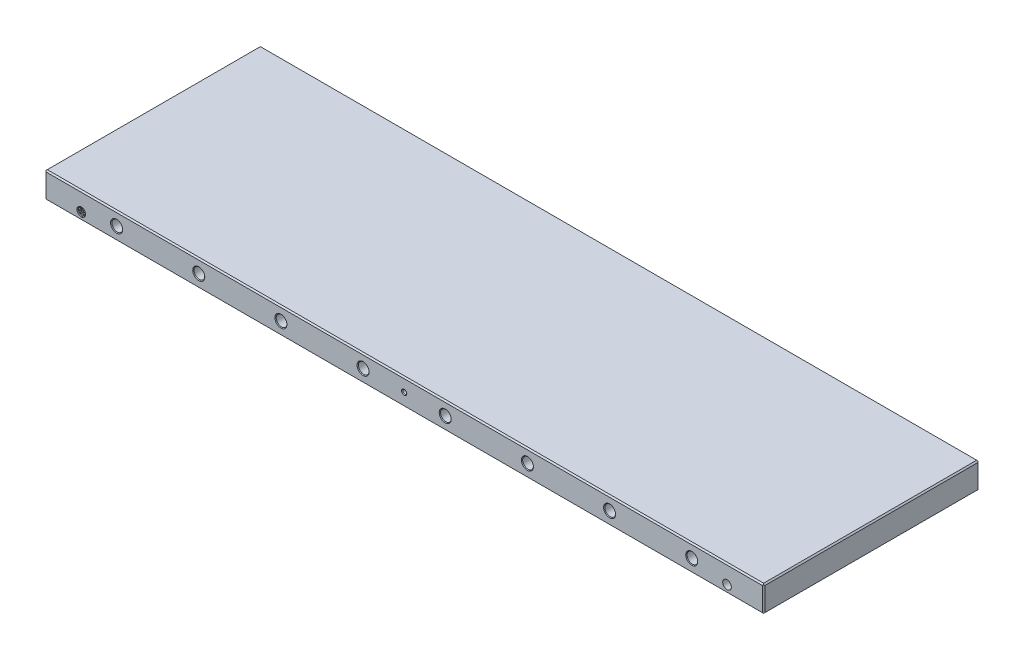
SolidWorks part; units mm, degrees
ref_plane "Front Plane" through (0, 0, 0) normal (0, 0, 1) x (1, 0, 0)
ref_plane "Top Plane" through (0, 0, 0) normal (0, 1, 0) x (1, 0, 0)
ref_plane "Right Plane" through (0, 0, 0) normal (1, 0, 0) x (0, 0, -1)
sketch "Sketch1" plane through (0, 0, 0) normal (0, 1, 0) x (1, 0, 0)
  line L1 (-275, 82.5) -> (275, 82.5)
  line L2 (-275, 82.5) -> (-275, -82.5)
  line L3 (-275, -82.5) -> (275, -82.5)
  line L4 (275, 82.5) -> (275, -82.5)
  line L5 (-275, 82.5) -> (275, -82.5) construction
  line L6 (-275, -82.5) -> (275, 82.5) construction
  point P0 (0, 0)
  dimension "D1" = 165
  dimension "D2" = 550
extrude "Boss-Extrude1" add sketch "Sketch1" along normal blind 20
sketch "Sketch2" plane through (0, 0, 82.5) normal (0, 0, 1) x (1, 0, 0)
  line L0 (-275, 10) -> (275, 10) construction
  line L1 (-275, 20) -> (-275, 0) construction
  line L2 (275, 20) -> (275, 0) construction
  circle A0 centre (-220, 10) radius 4.1
  circle A1 centre (-157.1429, 10) radius 4.1
  circle A2 centre (-94.2857, 10) radius 4.1
  circle A3 centre (-31.4286, 10) radius 4.1
  circle A4 centre (31.4286, 10) radius 4.1
  circle A5 centre (94.2857, 10) radius 4.1
  circle A6 centre (157.1429, 10) radius 4.1
  circle A7 centre (220, 10) radius 4.1
  dimension "D1" = 8.2
  dimension "D2" = 55
  dimension "D4" = 55
  dimension "D3" = 8
extrude "Cut-Extrude1" cut sketch "Sketch2" against normal blind 162
chamfer "Chamfer2" distance 0.5 angle 45 1 edges at (224.1, 10, 82.5)
chamfer "Chamfer3" distance 0.5 angle 45 7 edges at (161.2429, 10, 82.5) (98.3857, 10, 82.5) (35.5286, 10, 82.5) (-27.3286, 10, 82.5) (-90.1857, 10, 82.5) (-153.0429, 10, 82.5) (-215.9, 10, 82.5)
chamfer "Chamfer4" distance 1 angle 45 4 edges at (-275, 10, -82.5) (275, 10, -82.5) (275, 10, 82.5) (-275, 10, 82.5)
chamfer "Chamfer5" distance 1 angle 45 8 edges at (0, 0, 82.5) (-275, 0, 0) (0, 0, -82.5) (275, 0, 0) (275, 20, 0) (0, 20, -82.5) (-275, 20, 0) (0, 20, 82.5)
sketch "Sketch3" plane through (0, 0, 82.5) normal (0, 0, 1) x (1, 0, 0)
  line L0 (-274, 10) -> (274, 10) construction
  line L1 (274, 1) -> (274, 19) construction
  line L2 (-274, 19) -> (-274, 1) construction
  circle A0 centre (0, 10) radius 1.5
  point P5 (0, 10)
  dimension "D1" = 3
extrude "Cut-Extrude2" cut sketch "Sketch3" against normal blind 116
chamfer "Chamfer6" distance 0.5 angle 45 1 edges at (1.5, 10, 82.5)
sketch "Sketch5" plane through (0, 0, 82.5) normal (0, 0, 1) x (1, 0, 0)
  circle A0 centre (-247.02, 6) radius 3.3
  dimension "D1" = 6.6
sketch "Sketch6" plane through (0, 0, 82.5) normal (0, 0, 1) x (1, 0, 0)
  circle A0 centre (246.98, 6) radius 3.3
  dimension "D1" = 6.6
extrude "Cut-Extrude3" cut sketch "Sketch5" against normal blind 10
extrude "Cut-Extrude4" cut sketch "Sketch6" against normal blind 10
thread "Thread1" pitch 1 start angle 0, offset 0, length 10, pitch 1, diameter 6.6
ref_plane "Plane1" through (-250.32, 6, 82.5) normal (0, -1, 0) x (-1, 0, 0)
sketch "Thread Profile1" plane through (-250.32, 6, 82.5) normal (0, -1, 0) x (-1, 0, 0)
  line L0 (0, 0) -> (0, 1) construction
  line L11 (0, 0) -> (0, 0.875)
  line L12 (0, 0.875) -> (-0.5413, 0.5625)
  line L13 (-0.5413, 0.5625) -> (-0.5413, 0.3125)
  line L15 (-0.5413, 0.3125) -> (0, 0)
  line L17 (-0.5413, 0.4375) -> (0, 0.4375) construction
  point P2 (0, 0)
  dimension "Pitch" = 1
  dimension "Profile_Angle" = 60
  dimension "Profile_Land" = 0.25
  dimension "Profile_Height" = 0.5413
sketch "Sketch10" plane through (0, 0, -82.5) normal (0, 0, -1) x (-1, 0, 0)
  circle A0 centre (247, 6) radius 3.3
  circle A1 centre (-247, 6) radius 3.3
  dimension "D1" = 6.6
  dimension "D2" = 6.6
extrude "Cut-Extrude5" cut sketch "Sketch10" against normal blind 10
thread "Thread2" pitch 1 profile "Thread Profile2" start angle 0, offset 0, length 10, pitch 1, diameter 6.6
ref_plane "Plane2" through (243.7, 6, -72.5) normal (0, -1, 0) x (-1, 0, 0)
sketch "Thread Profile2" plane through (243.7, 6, -72.5) normal (0, -1, 0) x (-1, 0, 0)
  line L0 (0, 0) -> (0, 1) construction
  line L11 (0, 0) -> (0, 0.875)
  line L12 (0, 0.875) -> (-0.5413, 0.5625)
  line L13 (-0.5413, 0.5625) -> (-0.5413, 0.3125)
  line L15 (-0.5413, 0.3125) -> (0, 0)
  line L17 (-0.5413, 0.4375) -> (0, 0.4375) construction
  point P2 (0, 0)
  dimension "Pitch" = 1
  dimension "Profile_Angle" = 60
  dimension "Profile_Land" = 0.25
  dimension "Profile_Height" = 0.5413
thread "Thread3" pitch 1 profile "Thread Profile3" start angle 0, offset 0, length 10, pitch 1, diameter 6.6
ref_plane "Plane3" through (-250.3, 6, -72.5) normal (0, -1, 0) x (-1, 0, 0)
sketch "Thread Profile3" plane through (-250.3, 6, -72.5) normal (0, -1, 0) x (-1, 0, 0)
  line L0 (0, 0) -> (0, 1) construction
  line L11 (0, 0) -> (0, 0.875)
  line L12 (0, 0.875) -> (-0.5413, 0.5625)
  line L13 (-0.5413, 0.5625) -> (-0.5413, 0.3125)
  line L15 (-0.5413, 0.3125) -> (0, 0)
  line L17 (-0.5413, 0.4375) -> (0, 0.4375) construction
  point P2 (0, 0)
  dimension "Pitch" = 1
  dimension "Profile_Angle" = 60
  dimension "Profile_Land" = 0.25
  dimension "Profile_Height" = 0.5413
